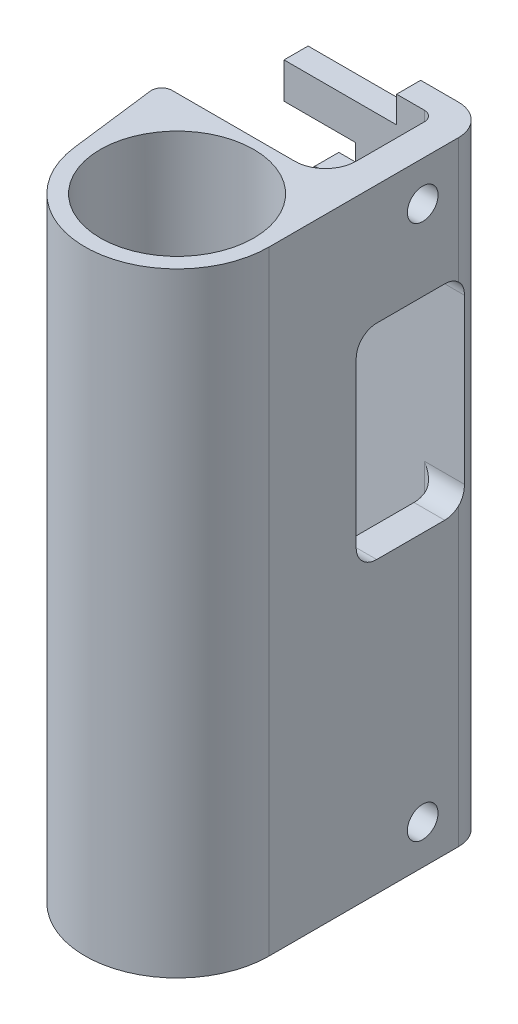
SolidWorks part; units mm, degrees
ref_plane "Спереди" through (0, 0, 0) normal (0, 0, 1) x (1, 0, 0)
ref_plane "Сверху" through (0, 0, 0) normal (0, 1, 0) x (1, 0, 0)
ref_plane "Справа" through (0, 0, 0) normal (1, 0, 0) x (0, 0, -1)
sketch "Эскиз1" plane through (0, 0, 0) normal (0, 1, 0) x (1, 0, 0)
  line L0 (9, 21.5) -> (6, 21.5)
  line L1 (6, 21.5) -> (6, 8.5)
  line L2 (6, 8.5) -> (-10.1328, 8.5)
  line L3 (-10.1328, 8.5) -> (-8.9305, -1.1166)
  line L4 (9, 0) -> (9, 21.5)
  arc A0 (-8.9305, -1.1166) -> (9, 0) centre (0, 0) ccw
extrude "Бобышка-Вытянуть1" add sketch "Эскиз1" against normal blind 11.7
sketch "Эскиз2" plane through (0, -11.7, 0) normal (0, -1, 0) x (1, 0, 0)
  line L0 (9, -8.5) -> (-10.1328, -8.5)
  line L1 (-10.1328, -8.5) -> (-8.9305, 1.1166)
  line L2 (9, 0) -> (9, -8.5)
  arc A0 (-8.9305, 1.1166) -> (9, 0) centre (0, 0) cw
extrude "Бобышка-Вытянуть2" add sketch "Эскиз2" along normal blind 20
sketch "Эскиз3" plane through (0, -11.7, 0) normal (0, -1, 0) x (1, 0, 0)
  line L0 (6, -19.15) -> (9, -19.15)
  line L1 (9, -19.15) -> (9, -21.5)
  line L2 (9, -21.5) -> (6, -21.5)
  line L3 (6, -21.5) -> (6, -19.15)
extrude "Бобышка-Вытянуть3" add sketch "Эскиз3" along normal blind 20
sketch "Эскиз4" plane through (0, -31.7, 0) normal (0, -1, 0) x (1, 0, 0)
  line L0 (6, -21.5) -> (6, -8.5)
  line L1 (6, -8.5) -> (-10.1328, -8.5)
  line L2 (-10.1328, -8.5) -> (-8.9305, 1.1166)
  line L3 (9, 0) -> (9, -21.5)
  line L4 (9, -21.5) -> (6, -21.5)
  arc A0 (-8.9305, 1.1166) -> (9, 0) centre (0, 0) cw
extrude "Бобышка-Вытянуть4" add sketch "Эскиз4" along normal blind 28.3
sketch "Эскиз5" plane through (6, 0, 0) normal (-1, 0, 0) x (0, 0, 1)
  line L0 (-21.5, -60) -> (-21.5, 0)
  line L1 (-21.5, 0) -> (-19.15, 0)
  line L2 (-19.15, 0) -> (-19.15, -60)
  line L3 (-19.15, -60) -> (-21.5, -60)
extrude "Бобышка-Вытянуть5" add sketch "Эскиз5" along normal blind 14.7
sketch "Эскиз6" plane through (0, 0, -21.5) normal (0, 0, -1) x (-1, 0, 0)
  line L0 (-2.3, 0) -> (-2.3, -2.6)
  line L1 (-2.3, -2.6) -> (8.7, -2.6)
  line L2 (8.7, -2.6) -> (8.7, 0)
  line L3 (8.7, 0) -> (-2.3, 0)
extrude "Вырез-Вытянуть1" cut sketch "Эскиз6" against normal up to next
sketch "Эскиз7" plane through (0, 0, -21.5) normal (0, 0, -1) x (-1, 0, 0)
  line L0 (8.7, -13.1) -> (8.7, -6.1)
  line L1 (8.7, -6.1) -> (1.7, -6.1)
  line L2 (1.7, -6.1) -> (1.7, -10.1)
  line L3 (1.7, -10.1) -> (5.7, -10.1)
  line L4 (5.7, -10.1) -> (8.7, -13.1)
extrude "Вырез-Вытянуть2" cut sketch "Эскиз7" against normal up to next
sketch "Эскиз8" plane through (0, 0, -21.5) normal (0, 0, -1) x (-1, 0, 0)
  line L0 (8.7, -44.4) -> (8.7, -36.9)
  line L1 (8.7, -36.9) -> (5.7, -39.9)
  line L2 (5.7, -39.9) -> (1.7, -39.9)
  line L3 (1.7, -39.9) -> (1.7, -41.4)
  line L4 (1.7, -41.4) -> (5.7, -41.4)
  line L5 (5.7, -41.4) -> (8.7, -44.4)
extrude "Вырез-Вытянуть3" cut sketch "Эскиз8" against normal up to next
hole_wizard "Диаметр отверстия Ø3.0 (3)1" positions "Эскиз10" profile "Эскиз9" hole size "Ø3.0" standard "Ansi Metric"
sketch "Эскиз10" plane through (9, 0, 0) normal (1, 0, 0) x (0, 0, -1)
  point P0 (15, -3.85)
  point P1 (15, -56.15)
sketch "Эскиз9" plane through (9, -3.85, -15) normal (0, 1, 0) x (0, 0, -1)
  line L0 (0, 0) -> (0, 19.1328)
  line L1 (0, 19.1328) -> (1.5, 19.1328)
  line L2 (1.5, 19.1328) -> (1.5, 0)
  line L5 (1.5, 0) -> (0, 0)
  line L11 (0, -6.35) -> (0, 107.95) construction
  dimension "Диаметр сквозного отверстия" = 3
  dimension "Глубина сквозного отверстия" = 19.1328
hole_wizard "Диаметр отверстия Ø3.0 (3)2" positions "Эскиз12" profile "Эскиз11" hole size "Ø3.0" standard "Ansi Metric"
sketch "Эскиз12" plane through (0, 0, -21.5) normal (0, 0, -1) x (-1, 0, 0)
  point P0 (5.3923, -21.25)
sketch "Эскиз11" plane through (-5.3923, -21.25, -21.5) normal (1, 0, 0) x (0, 1, 0)
  line L0 (0, 0) -> (0, 2.35)
  line L1 (0, 2.35) -> (1.5, 2.35)
  line L2 (1.5, 2.35) -> (1.5, 0)
  line L5 (1.5, 0) -> (0, 0)
  line L11 (0, -6.35) -> (0, 107.95) construction
  dimension "Диаметр сквозного отверстия" = 3
  dimension "Глубина сквозного отверстия" = 2.35
hole_wizard "Диаметр отверстия Ø15.0 (15)1" positions "Эскиз14" profile "Эскиз13" hole size "Ø15.0" standard "Ansi Metric"
sketch "Эскиз14" plane through (0, 0, 0) normal (0, 1, 0) x (1, 0, 0)
  point P0 (0, 0)
sketch "Эскиз13" plane through (0, 0, 0) normal (1, 0, 0) x (0, 0, 1)
  line L0 (0, 0) -> (0, 60)
  line L1 (0, 60) -> (7.5, 60)
  line L2 (7.5, 60) -> (7.5, 0)
  line L5 (7.5, 0) -> (0, 0)
  line L11 (0, -6.35) -> (0, 107.95) construction
  dimension "Диаметр сквозного отверстия" = 15
  dimension "Глубина сквозного отверстия" = 60
hole_wizard "Диаметр отверстия Ø3.0 (3)3" positions "Эскиз16" profile "Эскиз15" hole size "Ø3.0" standard "Ansi Metric"
sketch "Эскиз16" plane through (0, 0, -8.5) normal (0, 0, -1) x (-1, 0, 0)
  point P0 (5.3923, -21.25)
sketch "Эскиз15" plane through (-5.3923, -21.25, -8.5) normal (1, 0, 0) x (0, 1, 0)
  line L0 (0, 0) -> (0, 3.2872)
  line L1 (0, 3.2872) -> (1.5, 3.2872)
  line L2 (1.5, 3.2872) -> (1.5, 0)
  line L5 (1.5, 0) -> (0, 0)
  line L11 (0, -6.35) -> (0, 107.95) construction
  dimension "Диаметр сквозного отверстия" = 3
  dimension "Глубина сквозного отверстия" = 3.2872
ref_plane "Плоскость1" through (-9.8839, 0, 0) normal (-1, 0, 0) x (0, 0, 1)
hole_wizard "Диаметр отверстия Ø3.0 (3)4" positions "Эскиз18" profile "Эскиз17" hole size "Ø3.0" standard "Ansi Metric"
sketch "Эскиз18" plane through (-9.8839, 0, 0) normal (-1, 0, 0) x (0, 0, 1)
  point P0 (-5.0093, -13)
  point P1 (-5.0093, -47)
sketch "Эскиз17" plane through (-9.8839, -13, -5.0093) normal (0, 1, 0) x (0, 0, 1)
  line L0 (0, 0) -> (0, 4.3021)
  line L1 (0, 4.3021) -> (1.5, 4.3021)
  line L2 (1.5, 4.3021) -> (1.5, 0)
  line L5 (1.5, 0) -> (0, 0)
  line L11 (0, -6.35) -> (0, 107.95) construction
  dimension "Диаметр сквозного отверстия" = 3
  dimension "Глубина сквозного отверстия" = 4.3021
fillet "Скругление1" radius 1 3 edges at (6, -45.85, -19.15) (-10.1328, -30, -8.5) (6, -5.85, -19.15)
fillet "Скругление2" radius 2 4 edges at (7, -11.7, -19.15) (7.5, -31.7, -8.5) (7.5, -11.7, -8.5) (7, -31.7, -19.15)
fillet "Скругление3" radius 3 2 edges at (6, -44.85, -8.5) (9, -30, -21.5)
